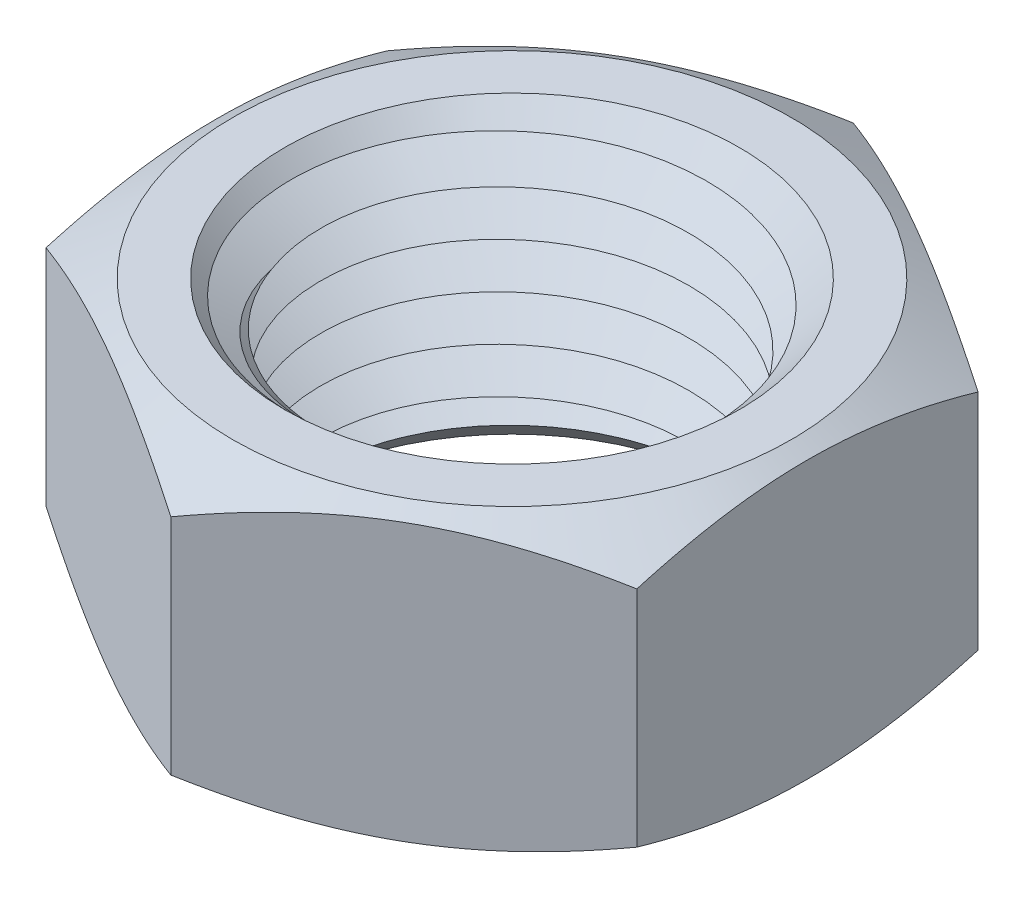
SolidWorks part; units mm, degrees
ref_plane "Plano frontal" through (0, 0, 0) normal (0, 0, 1) x (1, 0, 0)
ref_plane "Plano superior" through (0, 0, 0) normal (0, 1, 0) x (1, 0, 0)
ref_plane "Plano direito" through (0, 0, 0) normal (1, 0, 0) x (0, 0, -1)
sketch "Esboço1" plane through (0, 0, 0) normal (0, 1, 0) x (1, 0, 0)
  line L1 (0, 7.5056) -> (-6.5, 3.7528)
  line L2 (-6.5, 3.7528) -> (-6.5, -3.7528)
  line L3 (-6.5, -3.7528) -> (0, -7.5056)
  line L4 (0, -7.5056) -> (6.5, -3.7528)
  line L5 (6.5, -3.7528) -> (6.5, 3.7528)
  line L6 (6.5, 3.7528) -> (0, 7.5056)
  circle A0 centre (0, 0) radius 4
  circle A1 centre (0, 0) radius 6.5 construction
  dimension "D1" = 8
  dimension "D2" = 13
extrude "Extrusão1" add sketch "Esboço1" against normal blind 6.5
sketch "Esboço2" plane through (0, 0, 0) normal (0, 1, 0) x (1, 0, 0)
  circle A0 centre (0, 0) radius 6.143
extrude "Extrusão2" cut sketch "Esboço2" against normal blind 1 draft 60 flip side to cut
sketch "Esboço3" plane through (0, -6.5, 0) normal (0, -1, 0) x (1, 0, 0)
  circle A0 centre (0, 0) radius 6.1341
extrude "Extrusão3" cut sketch "Esboço3" against normal blind 1 draft 60 flip side to cut
sketch "Esboço4" plane through (0, 0, 0) normal (0, 1, 0) x (1, 0, 0)
  circle A0 centre (0, 0) radius 4 construction
  circle A1 centre (0, 0) radius 4
curve "Hélice/Espiral1" pitch 1 height 6.5 turns 6.5
sketch "Esboço5" plane through (0, 0, 0) normal (0, 0, 1) x (1, 0, 0)
  line L0 (-4, 0) -> (-4, 1) construction
  line L1 (4, 0) -> (-4, 0) construction
  line L2 (-4, 1) -> (-4.866, 0.5) construction
  line L3 (-4.866, 0.5) -> (-4, 0) construction
  line L4 (-4, 0.5) -> (-5.0146, 0.5) construction
  line L5 (-3.97, -0.052) -> (-3.97, 1.052)
  line L6 (-3.97, 1.052) -> (-4.926, 0.5)
  line L7 (-4.926, 0.5) -> (-3.97, -0.052)
  spline S0 degree 3 poles (-4, 0) (-4, -0.0209) (-3.7876, -0.0632) (-2.8813, -0.1262) (-1.5279, -0.1893) (0.0626, -0.2524) (1.6434, -0.3155) (2.9692, -0.3786) (3.8342, -0.4417) (4.1043, -0.5049) (3.7375, -0.568) (2.7907, -0.6311) (1.4109, -0.6942) (-0.1878, -0.7573) (-1.7574, -0.8204) (-3.0543, -0.8835) (-3.8772, -0.9466) (-4.0986, -1.0097) (-3.6839, -1.0728) (-2.6976, -1.1359) (-1.2927, -1.199) (0.3128, -1.2621) (1.8698, -1.3252) (3.1366, -1.3883) (3.9167, -1.4515) (4.089, -1.5146) (3.6269, -1.5777) (2.6019, -1.6408) (1.1732, -1.7039) (-0.4375, -1.767) (-1.9804, -1.8301) (-3.2159, -1.8932) (-3.9525, -1.9563) (-4.0757, -2.0194) (-3.5665, -2.0825) (-2.5038, -2.1456) (-1.0527, -2.2087) (0.5618, -2.2718) (2.0891, -2.335) (3.2923, -2.3981) (3.9846, -2.4612) (4.0585, -2.5243) (3.5027, -2.5874) (2.4034, -2.6505) (0.9311, -2.7136) (-0.6856, -2.7767) (-2.196, -2.8398) (-3.3656, -2.9029) (-4.013, -2.966) (-4.0376, -3.0291) (-3.4358, -3.0922) (-2.3008, -3.1553) (-0.8088, -3.2184) (0.8088, -3.2816) (2.3008, -3.3447) (3.4358, -3.4078) (4.0376, -3.4709) (4.013, -3.534) (3.3656, -3.5971) (2.196, -3.6602) (0.6856, -3.7233) (-0.9311, -3.7864) (-2.4034, -3.8495) (-3.5027, -3.9126) (-4.0585, -3.9757) (-3.9846, -4.0388) (-3.2923, -4.1019) (-2.0891, -4.165) (-0.5618, -4.2282) (1.0527, -4.2913) (2.5038, -4.3544) (3.5665, -4.4175) (4.0757, -4.4806) (3.9525, -4.5437) (3.2159, -4.6068) (1.9804, -4.6699) (0.4375, -4.733) (-1.1732, -4.7961) (-2.6019, -4.8592) (-3.6269, -4.9223) (-4.089, -4.9854) (-3.9167, -5.0485) (-3.1366, -5.1117) (-1.8698, -5.1748) (-0.3128, -5.2379) (1.2927, -5.301) (2.6976, -5.3641) (3.6839, -5.4272) (4.0986, -5.4903) (3.8772, -5.5534) (3.0543, -5.6165) (1.7574, -5.6796) (0.1878, -5.7427) (-1.4109, -5.8058) (-2.7907, -5.8689) (-3.7375, -5.932) (-4.1043, -5.9951) (-3.8342, -6.0583) (-2.9692, -6.1214) (-1.6434, -6.1845) (-0.0626, -6.2476) (1.5279, -6.3107) (2.8813, -6.3738) (3.7876, -6.4368) (4, -6.4791) (4, -6.5) knots 0 0 0 0 0.009709 0.019417 0.029126 0.038835 0.048544 0.058252 0.067961 0.07767 0.087379 0.097087 0.106796 0.116505 0.126214 0.135922 0.145631 0.15534 0.165049 0.174757 0.184466 0.194175 0.203883 0.213592 0.223301 0.23301 0.242718 0.252427 0.262136 0.271845 0.281553 0.291262 0.300971 0.31068 0.320388 0.330097 0.339806 0.349515 0.359223 0.368932 0.378641 0.38835 0.398058 0.407767 0.417476 0.427184 0.436893 0.446602 0.456311 0.466019 0.475728 0.485437 0.495146 0.504854 0.514563 0.524272 0.533981 0.543689 0.553398 0.563107 0.572816 0.582524 0.592233 0.601942 0.61165 0.621359 0.631068 0.640777 0.650485 0.660194 0.669903 0.679612 0.68932 0.699029 0.708738 0.718447 0.728155 0.737864 0.747573 0.757282 0.76699 0.776699 0.786408 0.796117 0.805825 0.815534 0.825243 0.834951 0.84466 0.854369 0.864078 0.873786 0.883495 0.893204 0.902913 0.912621 0.92233 0.932039 0.941748 0.951456 0.961165 0.970874 0.980583 0.990291 1 1 1 1 construction
  dimension "D1" = 1
  dimension "D2" = 60
  dimension "D3" = 0.03
chamfer "Chanfro1" distance 1 angle 45 2 edges at (0, -6.5, 4) (0, 0, 4)
sweep "Varredura de corte2" cut profiles "Esboço5" path "Hélice/Espiral1"
